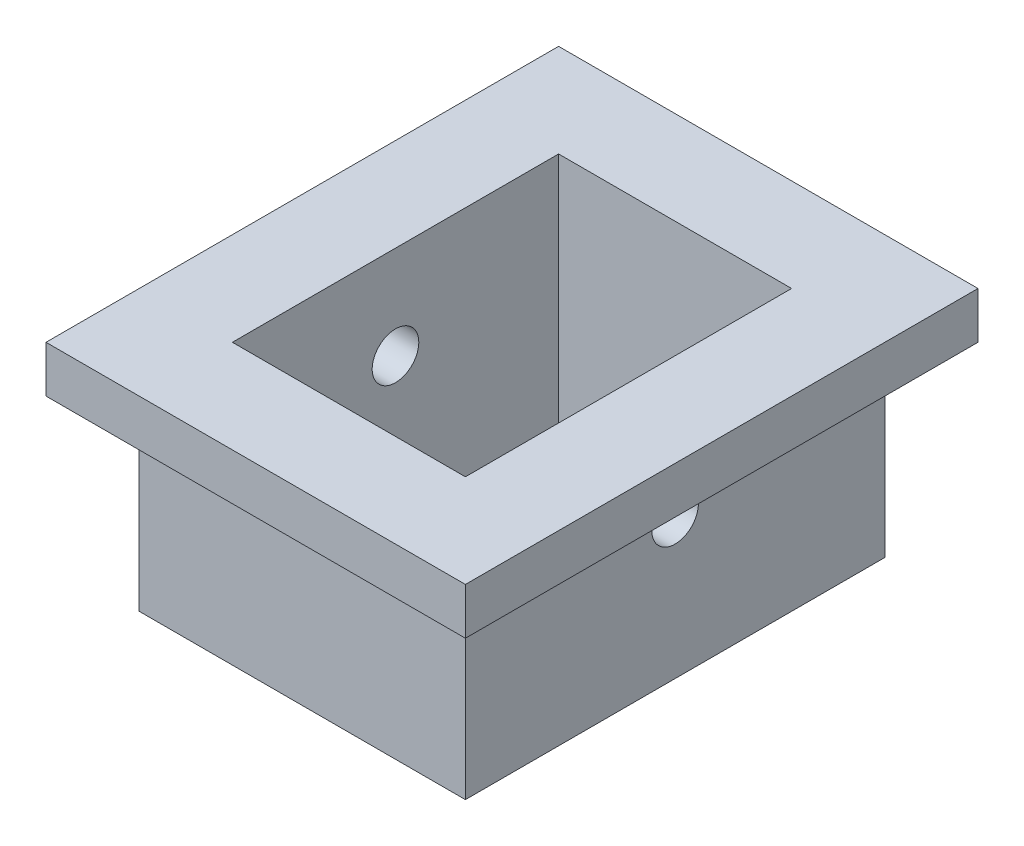
SolidWorks part; units mm, degrees
ref_plane "Front Plane" through (0, 0, 0) normal (0, 0, 1) x (1, 0, 0)
ref_plane "Top Plane" through (0, 0, 0) normal (0, 1, 0) x (1, 0, 0)
ref_plane "Right Plane" through (0, 0, 0) normal (1, 0, 0) x (0, 0, -1)
sketch "Sketch1" plane through (0, 0, 0) normal (0, 1, 0) x (1, 0, 0)
  line L0 (3.175, 4.445) -> (-3.175, 4.445)
  line L1 (4.445, -5.715) -> (-4.445, -5.715)
  line L2 (4.445, -5.715) -> (4.445, 5.715)
  line L3 (4.445, 5.715) -> (-4.445, 5.715)
  line L4 (-4.445, -5.715) -> (-4.445, 5.715)
  line L5 (4.445, -5.715) -> (-4.445, 5.715) construction
  line L6 (4.445, 5.715) -> (-4.445, -5.715) construction
  line L7 (-3.175, -4.445) -> (-3.175, 4.445)
  line L8 (3.175, -4.445) -> (-3.175, -4.445)
  line L9 (3.175, -4.445) -> (3.175, 4.445)
  point P0 (0, 0)
  dimension "D1" = 8.89
  dimension "D2" = 11.43
  dimension "D3" = 1.27
extrude "Boss-Extrude1" add sketch "Sketch1" along normal blind 6.35
sketch "Sketch2" plane through (0, 6.35, 0) normal (0, 1, 0) x (1, 0, 0)
  line L0 (4.445, 5.715) -> (-4.445, 5.715) construction
  line L4 (4.445, -5.715) -> (4.445, 5.715) construction
  line L5 (-4.445, -5.715) -> (4.445, -5.715) construction
  line L6 (-4.445, 5.715) -> (-4.445, -5.715) construction
  line L7 (4.445, 5.715) -> (-4.445, 5.715)
  line L13 (4.445, -5.715) -> (4.445, 5.715)
  line L14 (-4.445, -5.715) -> (4.445, -5.715)
  line L15 (-4.445, 5.715) -> (-4.445, -5.715)
  line L16 (-5.715, 6.985) -> (-5.715, -6.985)
  line L17 (-5.715, -6.985) -> (5.715, -6.985)
  line L18 (5.715, -6.985) -> (5.715, 6.985)
  line L19 (5.715, 6.985) -> (-5.715, 6.985)
  line L20 (-5.715, 6.985) -> (-5.715, -6.985)
  line L21 (-5.715, -6.985) -> (5.715, -6.985)
  line L22 (5.715, -6.985) -> (5.715, 6.985)
  line L23 (5.715, 6.985) -> (-5.715, 6.985)
  dimension "D1" = 1.27
extrude "Boss-Extrude2" add sketch "Sketch2" against normal blind 1.27
sketch "Sketch3" plane through (3.175, 0, 0) normal (-1, 0, 0) x (0, 0, 1)
  line L0 (4.445, 0) -> (-4.445, 0) construction
  circle A0 centre (0, 3.81) radius 0.635
  dimension "D1" = 1.27
  dimension "D2" = 3.81
extrude "Cut-Extrude1" cut sketch "Sketch3" against normal through all both and the other way through all
